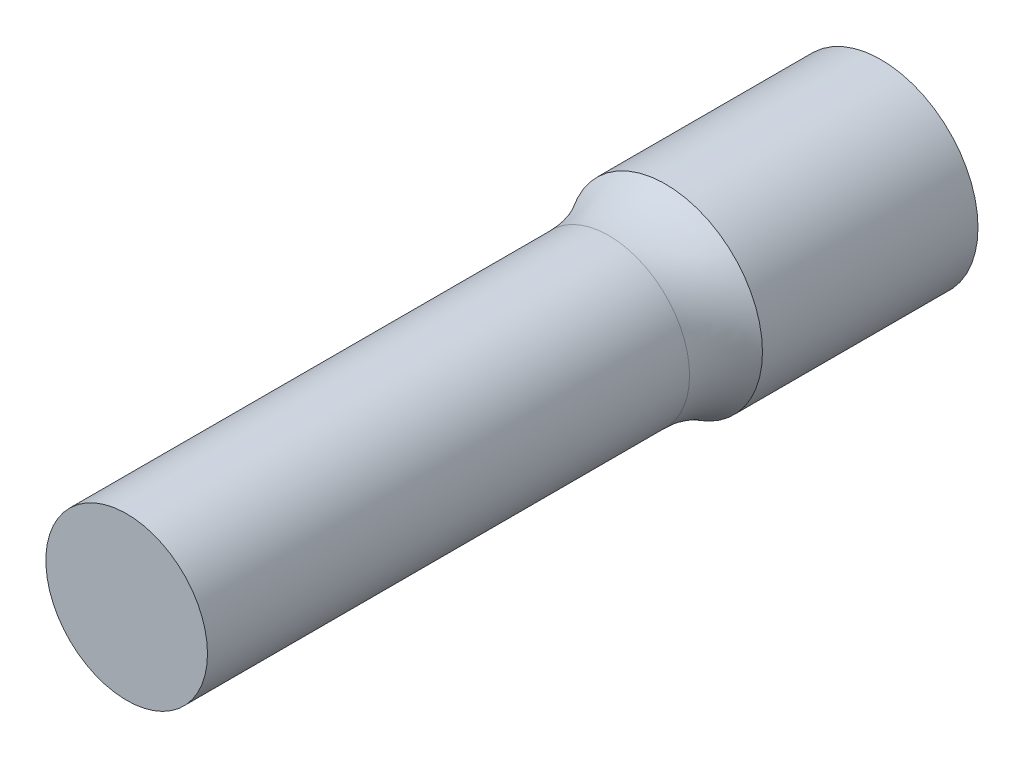
SolidWorks part; units mm, degrees
ref_plane "Front Plane" through (0, 0, 0) normal (0, 0, 1) x (1, 0, 0)
ref_plane "Top Plane" through (0, 0, 0) normal (0, 1, 0) x (1, 0, 0)
ref_plane "Right Plane" through (0, 0, 0) normal (1, 0, 0) x (0, 0, -1)
sketch "Sketch1" plane through (0, 0, 0) normal (0, 0, 1) x (1, 0, 0)
  circle A0 centre (0, 0) radius 9
  dimension "D1" = 18
extrude "Boss-Extrude1" add sketch "Sketch1" along normal blind 70
sketch "Sketch2" plane through (0, 0, 0) normal (0, 0, -1) x (-1, 0, 0)
  circle A0 centre (0, 0) radius 2.5
  dimension "D1" = 5
extrude "Cut-Extrude1" cut sketch "Sketch2" against normal blind 15
sketch "Sketch3" plane through (0, 0, 70) normal (0, 0, 1) x (1, 0, 0)
  circle A0 centre (0, 0) radius 9
  circle A1 centre (0, 0) radius 7.5
  circle M2 centre (0, 0) radius 9
  dimension "D1" = 15
  dimension "D2" = 1.5
extrude "Cut-Extrude2" cut sketch "Sketch3" against normal blind 50 contours A1 M2 region at (-8.7454, 0, 70)
fillet "Fillet1" radius 10 1 edges at (7.5, 0, 20)
